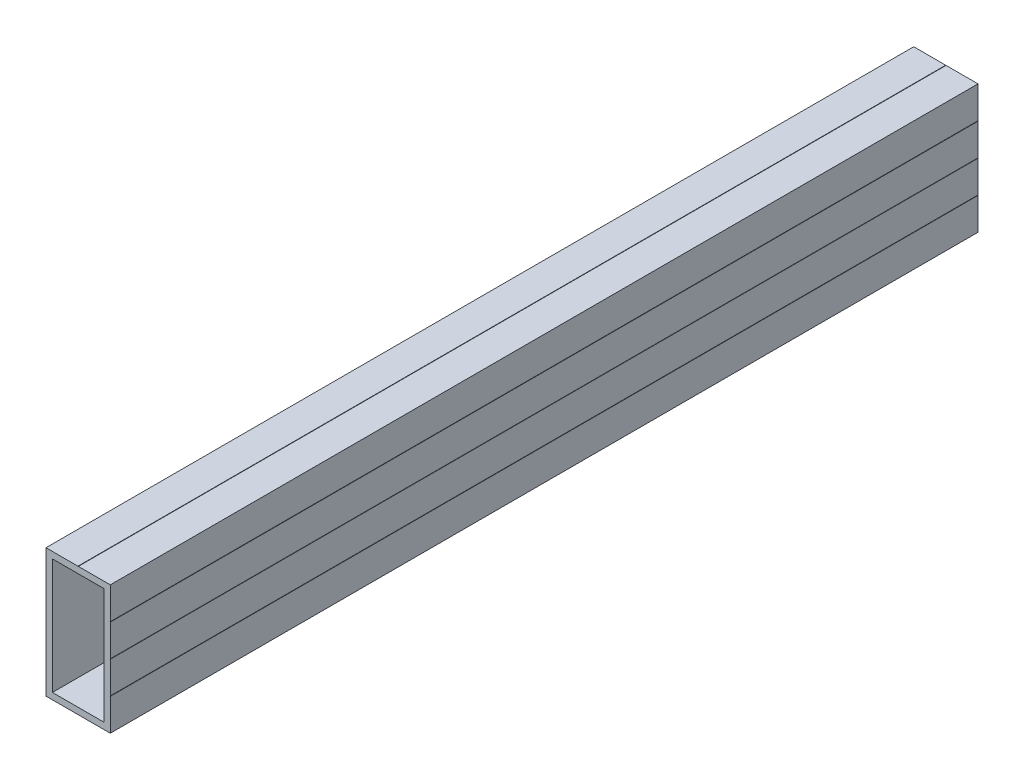
SolidWorks part; units mm, degrees
ref_plane "Front Plane" through (0, 0, 0) normal (0, 0, 1) x (1, 0, 0)
ref_plane "Top Plane" through (0, 0, 0) normal (0, 1, 0) x (1, 0, 0)
ref_plane "Right Plane" through (0, 0, 0) normal (1, 0, 0) x (0, 0, -1)
ref_plane "Plane1" through (12.7, 0, 0) normal (1, 0, 0) x (0, 0, -1)
sketch "Sketch1" plane through (12.7, 0, 0) normal (1, 0, 0) x (0, 0, -1)
  line L0 (-749.3, 25.4) -> (-749.3, -25.4)
  line L1 (-749.3, -25.4) -> (749.3, -25.4)
  line L2 (749.3, -25.4) -> (749.3, 25.4)
  line L3 (749.3, 25.4) -> (-749.3, 25.4)
extrude "Boss-Extrude1" add sketch "Sketch1" against normal blind 25.4
sketch "Sketch2" plane through (0, 0, 749.3) normal (0, 0, 1) x (1, 0, 0)
  line L0 (0.0762, 25.4) -> (-0.0762, 25.4)
  line L1 (-0.0762, 25.4) -> (0.0762, 25.2476)
  line L2 (0.0762, 25.2476) -> (0.0762, 25.4)
extrude "Cut-Extrude1" cut sketch "Sketch2" against normal blind 1498.6
sketch "Sketch3" plane through (0, 0, 749.3) normal (0, 0, 1) x (1, 0, 0)
  line L0 (12.7, 12.6238) -> (12.7, 12.7762)
  line L1 (12.7, 12.7762) -> (12.5476, 12.7762)
  line L2 (12.5476, 12.7762) -> (12.7, 12.6238)
extrude "Cut-Extrude2" cut sketch "Sketch3" against normal through all
sketch "Sketch4" plane through (0, 0, 749.3) normal (0, 0, 1) x (1, 0, 0)
  line L0 (12.7, -0.0762) -> (12.7, 0.0762)
  line L1 (12.7, 0.0762) -> (12.5476, -0.0762)
  line L2 (12.5476, -0.0762) -> (12.7, -0.0762)
extrude "Cut-Extrude3" cut sketch "Sketch4" against normal blind 1498.6
sketch "Sketch5" plane through (0, 0, 749.3) normal (0, 0, 1) x (1, 0, 0)
  line L0 (12.7, -12.7762) -> (12.7, -12.6238)
  line L1 (12.7, -12.6238) -> (12.5476, -12.6238)
  line L2 (12.5476, -12.6238) -> (12.7, -12.7762)
extrude "Cut-Extrude4" cut sketch "Sketch5" against normal blind 1498.6
sketch "Sketch6" plane through (0, 0, 749.3) normal (0, 0, 1) x (1, 0, 0)
  line L0 (0.0762, -25.4) -> (-0.0762, -25.2476)
  line L1 (-0.0762, -25.2476) -> (-0.0762, -25.4)
  line L2 (-0.0762, -25.4) -> (0.0762, -25.4)
extrude "Cut-Extrude5" cut sketch "Sketch6" against normal through all
sketch "Sketch7" plane through (0, 0, 749.3) normal (0, 0, 1) x (1, 0, 0)
  line L0 (-12.7, -12.6238) -> (-12.7, -12.7762)
  line L1 (-12.7, -12.7762) -> (-12.5476, -12.7762)
  line L2 (-12.5476, -12.7762) -> (-12.7, -12.6238)
extrude "Cut-Extrude6" cut sketch "Sketch7" against normal through all
sketch "Sketch8" plane through (0, 0, 749.3) normal (0, 0, 1) x (1, 0, 0)
  line L0 (-12.7, 0.0762) -> (-12.7, -0.0762)
  line L1 (-12.7, -0.0762) -> (-12.5476, 0.0762)
  line L2 (-12.5476, 0.0762) -> (-12.7, 0.0762)
extrude "Cut-Extrude7" cut sketch "Sketch8" against normal blind 1498.6
sketch "Sketch9" plane through (0, 0, 749.3) normal (0, 0, 1) x (1, 0, 0)
  line L0 (-12.7, 12.7762) -> (-12.7, 12.6238)
  line L1 (-12.7, 12.6238) -> (-12.5476, 12.6238)
  line L2 (-12.5476, 12.6238) -> (-12.7, 12.7762)
extrude "Cut-Extrude8" cut sketch "Sketch9" against normal blind 1498.6
sketch "Sketch10" plane through (0, 0, 749.3) normal (0, 0, 1) x (1, 0, 0)
  line L0 (10.16, -22.86) -> (10.16, 22.86)
  line L1 (10.16, 22.86) -> (-10.16, 22.86)
  line L2 (-10.16, 22.86) -> (-10.16, -22.86)
  line L3 (-10.16, -22.86) -> (10.16, -22.86)
extrude "Cut-Extrude9" cut sketch "Sketch10" against normal through all
draft "Draft1" type of draft neutral plane draft angle 45 faces to draft 1 face at (0.0762, 25.3238, 0) neutral plane through (-12.7, 25.4, -749.3) neutral plane normal (0, 1, 0) parameters "D1"=45
draft "Draft2" type of draft neutral plane draft angle 45 faces to draft 1 face at (12.6238, 12.7762, 0) neutral plane through (12.7, 0, 0) neutral plane normal (1, 0, 0) parameters "D1"=45
draft "Draft3" type of draft neutral plane draft angle 45 faces to draft 1 face at (-0.0762, -25.3238, 0) neutral plane through (-12.7, -25.4, 749.3) neutral plane normal (0, -1, 0) parameters "D1"=45
draft "Draft4" type of draft neutral plane draft angle 45 faces to draft 1 face at (-12.6238, -12.7762, 0) neutral plane through (-12.7, 0, 0) neutral plane normal (-1, 0, 0) parameters "D1"=45
draft "Draft5" type of draft neutral plane draft angle 45 faces to draft 2 face at (12.6238, -12.6238, 0) face at (12.6238, 0, 0) neutral plane through (12.7, 0, 0) neutral plane normal (1, 0, 0) parameters "D1"=45
draft "Draft6" type of draft neutral plane draft angle 45 faces to draft 2 face at (-12.6238, 0, 0) face at (-12.6238, 12.6238, 0) neutral plane through (-12.7, 0, 0) neutral plane normal (-1, 0, 0) parameters "D1"=45
sketch "Sketch11" plane through (0, 0, -749.3) normal (0, 0, -1) x (-1, 0, 0)
  line L1 (28.0564, 44.6652) -> (-33.9059, 44.6652)
  line L2 (28.0564, 44.6652) -> (28.0564, -44.0138)
  line L3 (28.0564, -44.0138) -> (-33.9059, -44.0138)
  line L4 (-33.9059, 44.6652) -> (-33.9059, -44.0138)
extrude "Cut-Extrude10" cut sketch "Sketch11" against normal blind 1155.7
